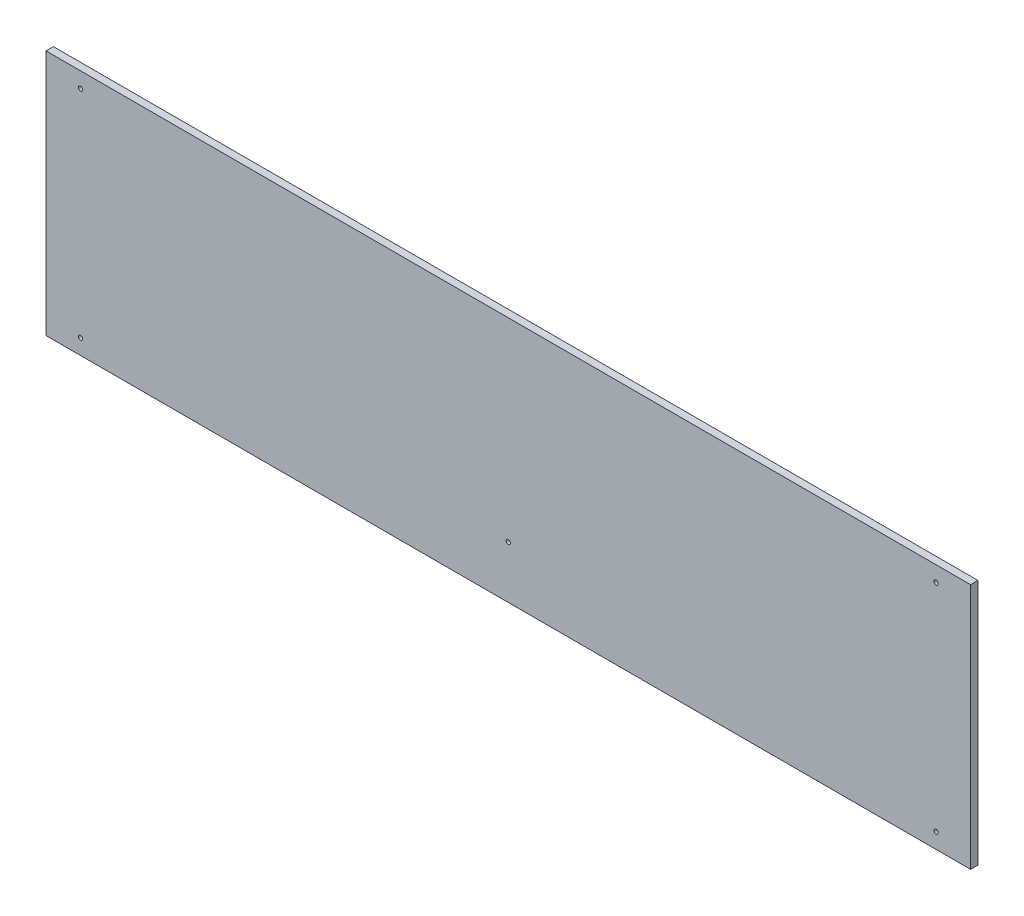
SolidWorks part; units mm, degrees
ref_plane "Front Plane" through (0, 0, 0) normal (0, 0, 1) x (1, 0, 0)
ref_plane "Top Plane" through (0, 0, 0) normal (0, 1, 0) x (1, 0, 0)
ref_plane "Right Plane" through (0, 0, 0) normal (1, 0, 0) x (0, 0, -1)
sketch "Sketch1" plane through (0, 0, 0) normal (0, 0, 1) x (1, 0, 0)
  line L1 (750, -200) -> (-750, -200)
  line L2 (750, -200) -> (750, 200)
  line L3 (750, 200) -> (-750, 200)
  line L4 (-750, -200) -> (-750, 200)
  line L5 (750, -200) -> (-750, 200) construction
  line L6 (750, 200) -> (-750, -200) construction
  point P0 (0, 0)
  dimension "D1" = 1500
  dimension "D2" = 400
extrude "RawMaterial" add sketch "Sketch1" along normal blind 12
hole_wizard "Ø7.0 (7) Frame Mount Holes" positions "Sketch3" profile "Sketch4" hole size "Ø7.0" standard "ANSI Metric" end condition through all
sketch "Sketch3" plane through (0, 0, 0) normal (0, 0, -1) x (-1, 0, 0)
  line L0 (750, -200) -> (-750, -200) construction
  line L1 (750, 200) -> (750, -200) construction
  point P0 (-694, 175)
  point P2 (-694, -175)
  point P4 (694, -175)
  point P6 (694, 175)
  point P21 (0, -115)
  dimension "D1" = 25
  dimension "D2" = 56
  dimension "D3" = 375
  dimension "D4" = 1444
  dimension "D5" = 85
sketch "Sketch4" plane through (694, 175, 0) normal (1, 0, 0) x (0, 1, 0)
  line L0 (0, 0) -> (0, 12)
  line L1 (0, 12) -> (3.5, 12)
  line L2 (3.5, 12) -> (3.5, 0)
  line L5 (3.5, 0) -> (0, 0)
  line L11 (0, -6.35) -> (0, 107.95) construction
  dimension "Thru Hole Dia." = 7
  dimension "Thru Hole Depth" = 12
